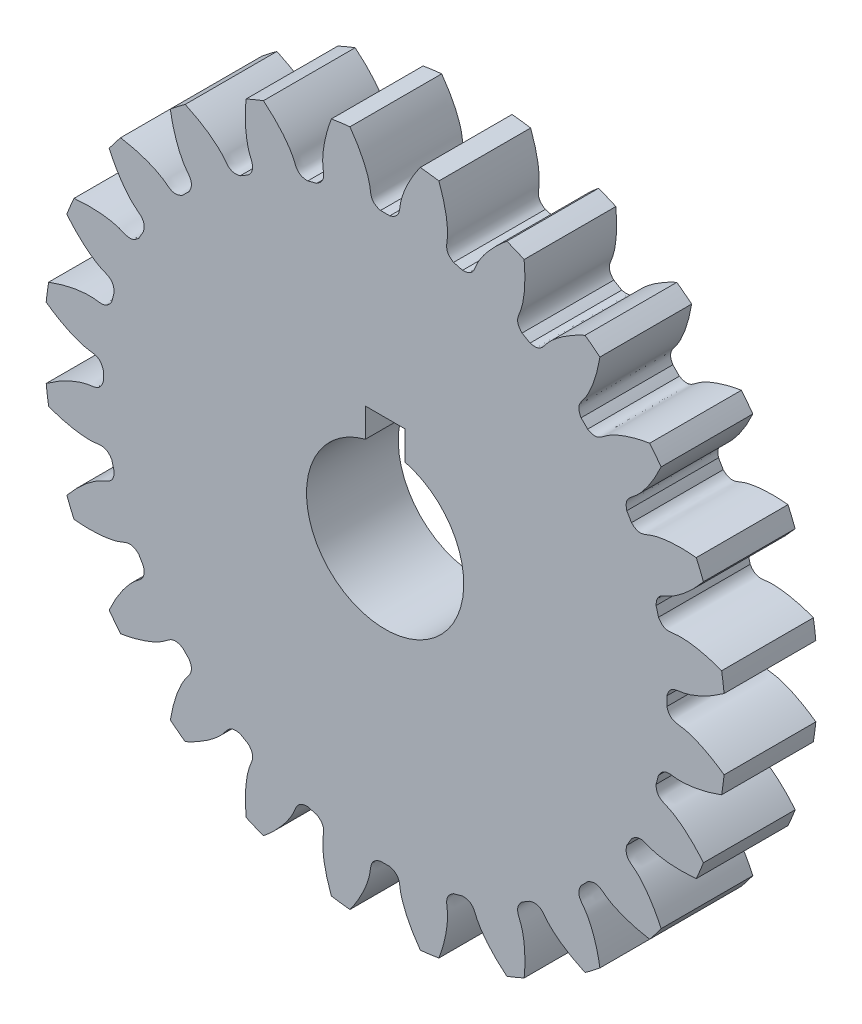
SolidWorks part; units mm, degrees
ref_plane "前视基准面" through (0, 0, 0) normal (0, 0, 1) x (1, 0, 0)
ref_plane "上视基准面" through (0, 0, 0) normal (0, 1, 0) x (1, 0, 0)
ref_plane "右视基准面" through (0, 0, 0) normal (1, 0, 0) x (0, 0, -1)
sketch "草图1" plane through (0, 0, 0) normal (0, 0, 1) x (1, 0, 0)
  circle A0 centre (0, 0) radius 26
extrude "凸台-拉伸1" add sketch "草图1" along normal blind 7 contours A0
ref_axis "基准轴1" through (0, 0, -0.5) along (0, 0, 1)
sketch "草图2" plane through (0, 0, 0) normal (0, 0, 1) x (1, 0, 0)
  line L0 (0, 0) -> (0, 26) construction
  circle A0 centre (0, 0) radius 26 construction
  arc A1 (0.3537, 21.4971) -> (-0.3537, 21.4971) centre (0, 0) ccw
  arc A2 (6.2312, 29.3882) -> (-6.2312, 29.3882) centre (0, 0) ccw
  spline S0 degree 3 poles (0.3537, 21.4971) (1.1358, 21.7137) (1.0781, 22.2314) (1.1726, 22.7454) (1.1861, 22.8117) (1.2029, 22.8865) (1.2234, 22.9697) (1.2478, 23.0612) (1.2766, 23.1609) (1.31, 23.2686) (1.3484, 23.3842) (1.3922, 23.5075) (1.4416, 23.6383) (1.4969, 23.7765) (1.5585, 23.9218) (1.6267, 24.0742) (1.7018, 24.2333) (1.784, 24.3989) (1.8737, 24.5709) (1.9712, 24.7489) (2.0767, 24.9328) (2.1904, 25.1223) (2.3128, 25.3171) (2.444, 25.517) (2.5842, 25.7216) (2.7338, 25.9308) (2.8929, 26.1441) (3.0617, 26.3614) (3.2406, 26.5822) (3.4296, 26.8063) (3.6291, 27.0334) (3.8391, 27.2631) (4.0599, 27.495) (4.2917, 27.729) (4.5345, 27.9645) (4.7886, 28.2013) (5.0542, 28.4389) (5.3312, 28.6771) (5.7208, 28.9987) (6.0238, 29.2338) (6.2312, 29.3882) knots 0 0 0 0 0.143961 0.149818 0.156577 0.164236 0.172796 0.182258 0.19262 0.203884 0.216049 0.229115 0.243082 0.25795 0.273719 0.290389 0.30796 0.326433 0.345806 0.366081 0.387257 0.409333 0.432311 0.45619 0.48097 0.506651 0.533234 0.560717 0.589101 0.618387 0.648574 0.679661 0.71165 0.74454 0.778331 0.813023 0.848616 0.885111 0.922506 1 1 1 1
  spline S1 degree 3 poles (-0.3537, 21.4971) (-1.1358, 21.7137) (-1.0781, 22.2314) (-1.1726, 22.7454) (-1.1861, 22.8117) (-1.2029, 22.8865) (-1.2234, 22.9697) (-1.2478, 23.0612) (-1.2766, 23.1609) (-1.31, 23.2686) (-1.3484, 23.3842) (-1.3922, 23.5075) (-1.4416, 23.6383) (-1.4969, 23.7765) (-1.5585, 23.9218) (-1.6267, 24.0742) (-1.7018, 24.2333) (-1.784, 24.3989) (-1.8737, 24.5709) (-1.9712, 24.7489) (-2.0767, 24.9328) (-2.1904, 25.1223) (-2.3128, 25.3171) (-2.444, 25.517) (-2.5842, 25.7216) (-2.7338, 25.9308) (-2.8929, 26.1441) (-3.0617, 26.3614) (-3.2406, 26.5822) (-3.4296, 26.8063) (-3.6291, 27.0334) (-3.8391, 27.2631) (-4.0599, 27.495) (-4.2917, 27.729) (-4.5345, 27.9645) (-4.7886, 28.2013) (-5.0542, 28.4389) (-5.3312, 28.6771) (-5.7208, 28.9987) (-6.0238, 29.2338) (-6.2312, 29.3882) knots 0 0 0 0 0.143961 0.149818 0.156577 0.164236 0.172796 0.182258 0.19262 0.203884 0.216049 0.229115 0.243082 0.25795 0.273719 0.290389 0.30796 0.326433 0.345806 0.366081 0.387257 0.409333 0.432311 0.45619 0.48097 0.506651 0.533234 0.560717 0.589101 0.618387 0.648574 0.679661 0.71165 0.74454 0.778331 0.813023 0.848616 0.885111 0.922506 1 1 1 1
extrude "切除-拉伸1" cut sketch "草图2" along normal through all
pattern_circular "阵列(圆周)1" count 24 every 15 about axis through (0, 0, -0.5) along (0, 0, 1) of "切除-拉伸1"
sketch "草图3" plane through (0, 0, 0) normal (0, 0, 1) x (1, 0, 0)
  circle A0 centre (0, 0) radius 24 construction
  dimension "Dn" = 48
sketch "草图4" plane through (0, 0, 7) normal (0, 0, 1) x (1, 0, 0)
  line L0 (-1.5, 4) -> (-1.5, 5.8095) construction
  line L1 (-1.5, 4) -> (1.5, 4) construction
  line L2 (-1.5, 5.8095) -> (-1.5, 8)
  line L3 (-1.5, 8) -> (1.5, 8)
  line L4 (1.5, 5.8095) -> (1.5, 8)
  line L5 (-1.5, 4) -> (1.5, 8) construction
  line L6 (-1.5, 8) -> (1.5, 4) construction
  line L7 (1.5, 4) -> (1.5, 5.8095) construction
  arc A0 (-1.5, 5.8095) -> (1.5, 5.8095) centre (0, 0) ccw
  arc A1 (1.5, 5.8095) -> (0, 6) centre (0, 0) ccw construction
  arc A2 (0, 6) -> (-1.5, 5.8095) centre (0, 0) ccw construction
  point P3 (0, 6)
  dimension "D1" = 12
  dimension "D2" = 4
  dimension "D3" = 3
extrude "切除-拉伸2" cut sketch "草图4" against normal up to next
